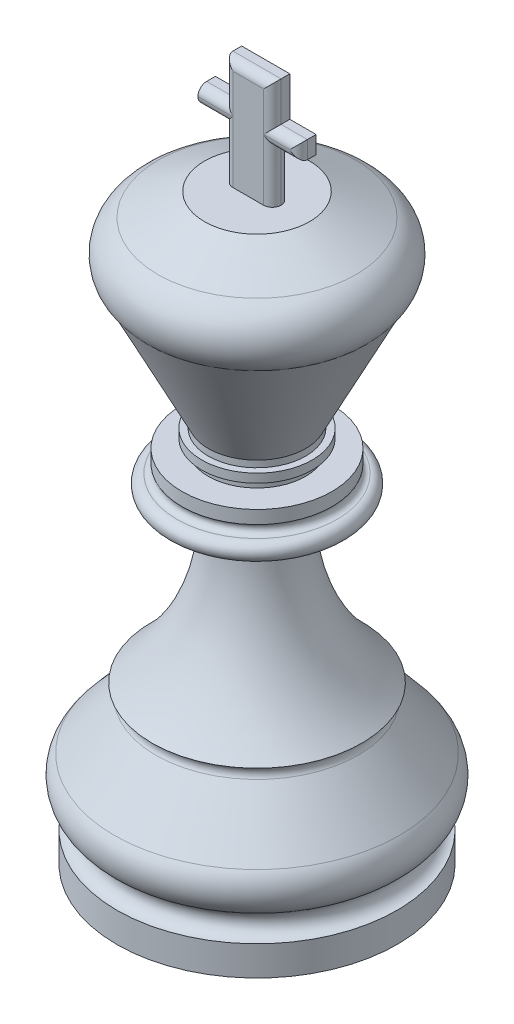
SolidWorks part; units mm, degrees
ref_plane "Ön Düzlem" through (0, 0, 0) normal (0, 0, 1) x (1, 0, 0)
ref_plane "Üst Düzlem" through (0, 0, 0) normal (0, 1, 0) x (1, 0, 0)
ref_plane "Sağ Düzlem" through (0, 0, 0) normal (1, 0, 0) x (0, 0, -1)
sketch "Çizim1" plane through (0, 0, 0) normal (0, 0, 1) x (1, 0, 0)
  line L0 (0, 0) -> (16, 0)
  line L1 (16, 0) -> (16, 3.3888)
  line L2 (0, 0) -> (0, 66.5)
  line L10 (12.4495, 57.5506) -> (5.5647, 43.8402)
  line L11 (5.5647, 43.8402) -> (5.5647, 43.0902)
  line L12 (5.5647, 43.0902) -> (6.3147, 43.0902)
  line L13 (6.3147, 43.0902) -> (6.3147, 42.0902)
  line L14 (6.3147, 42.0902) -> (5.5647, 42.0902)
  line L15 (5.5647, 42.0902) -> (5.5647, 41.0902)
  line L16 (5.5647, 41.0902) -> (8.5647, 41.0902)
  line L17 (8.5647, 41.0902) -> (8.5647, 39.5902)
  line L18 (9.1413, 36.5901) -> (4.8989, 36.5901)
  line L19 (0, 88.0422) -> (0, -26.16) construction
  line L20 (6, 66.5) -> (11.3125, 63.9194)
  line L21 (11.5469, 16.4939) -> (16.2687, 10.9194)
  line L22 (6, 66.5) -> (0, 66.5)
  arc A0 (12.4495, 57.5506) -> (11.3125, 63.9194) centre (9.5647, 60.3215) ccw
  arc A3 (4.8989, 36.5901) -> (11.9869, 17.9145) centre (27.1403, 34.3486) ccw
  arc A4 (15.3441, 5.9649) -> (16, 3.3888) centre (16.0006, 4.7605) ccw
  arc A5 (15.3441, 5.9649) -> (16.2687, 10.9194) centre (13.7887, 8.8187) ccw
  arc A6 (11.9869, 17.9145) -> (11.5469, 16.4939) centre (12.2576, 17.0522) ccw
  arc A7 (9.1413, 36.5901) -> (9.1413, 38.6202) centre (9.1413, 37.6052) ccw
  arc A8 (8.5647, 39.5902) -> (9.1413, 38.6202) centre (9.0914, 39.2469) ccw
  dimension "D16" = 4
  dimension "D2" = 16
  dimension "D9" = 0.75
  dimension "D10" = 0.75
  dimension "D11" = 1
  dimension "D12" = 0.75
  dimension "D13" = 1
  dimension "D14" = 1.5
  dimension "D15" = 3
  dimension "D17" = 4
revolve "Döndür2" add sketch "Çizim1" angle 360 about L19
sketch "Çizim2" plane through (0, 0, 0) normal (0, 0, 1) x (1, 0, 0)
  line L0 (0, 84.1155) -> (0, 62.16) construction
  line L1 (-2.75, 66.5) -> (-2.75, 72.5)
  line L2 (6, 66.5) -> (-6, 66.5) construction
  line L3 (-2.75, 72.5) -> (-5.75, 72.5)
  line L4 (-5.75, 72.5) -> (-5.75, 74.5)
  line L5 (-5.75, 74.5) -> (-2.75, 74.5)
  line L6 (-2.75, 74.5) -> (-2.75, 79)
  line L7 (-2.75, 79) -> (2.75, 79)
  line L8 (2.75, 74.5) -> (2.75, 79)
  line L9 (5.75, 74.5) -> (2.75, 74.5)
  line L10 (5.75, 72.5) -> (5.75, 74.5)
  line L11 (2.75, 72.5) -> (5.75, 72.5)
  line L12 (2.75, 66.5) -> (2.75, 72.5)
  line L13 (-2.75, 66.5) -> (2.75, 66.5)
  point P12 (0, 79)
  dimension "D1" = 6
  dimension "D2" = 3
  dimension "D3" = 2
  dimension "D4" = 4.5
  dimension "D5" = 3
  dimension "D6" = 5.5
  dimension "D7" = 6
  dimension "D8" = 4.5
  dimension "D9" = 2
  dimension "D10" = 5.5
  dimension "D11" = 3
extrude "Yükseklik-Ekstrüzyon1" add sketch "Çizim2" along normal blind 1 and the other way blind 1
fillet "Radyus1" radius 1 11 edges at (-2.75, 69.5, 1) (-4.25, 72.5, 1) (-4.25, 74.5, 1) (-2.75, 76.75, 1) (0, 79, 1) (2.75, 76.75, 1) (4.25, 74.5, 1) (5.75, 73.5, 1) (4.25, 72.5, 1) (2.75, 69.5, -1) (2.75, 69.5, 1)
